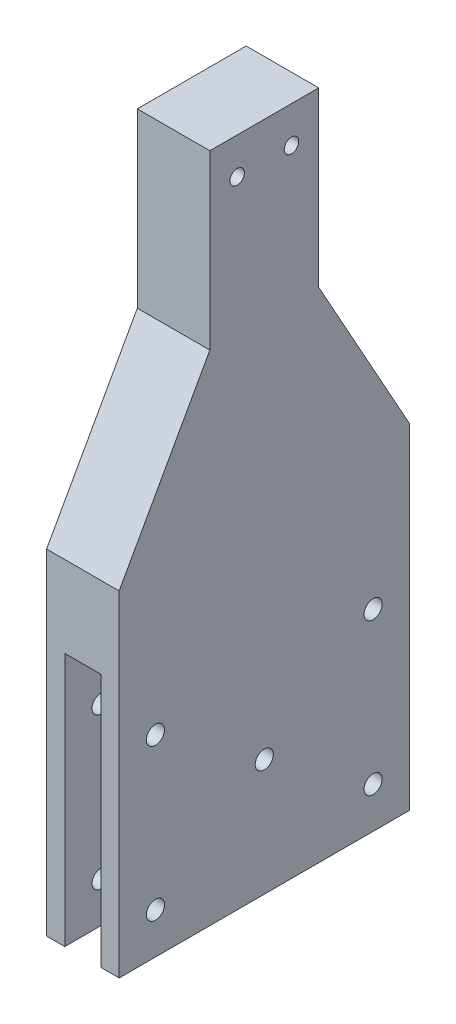
SolidWorks part; units mm, degrees
ref_plane "Plan de face" through (0, 0, 0) normal (0, 0, 1) x (1, 0, 0)
ref_plane "Plan de dessus" through (0, 0, 0) normal (0, 1, 0) x (1, 0, 0)
ref_plane "Plan de droite" through (0, 0, 0) normal (1, 0, 0) x (0, 0, -1)
sketch "Support Balise" plane through (0, 0, 0) normal (0, 0, 1) x (1, 0, 0)
  line L1 (0, 0) -> (20, 0)
  line L2 (0, 0) -> (0, 350)
  line L3 (0, 350) -> (20, 350)
  line L4 (20, 0) -> (20, 350)
  dimension "D1" = 20
  dimension "D2" = 350
extrude "Support balise bossage" add sketch "Support Balise" along normal blind 80
sketch "Esquisse3" plane through (0, 350, 0) normal (0, 1, 0) x (1, 0, 0)
  line L0 (20, 0) -> (20, -80)
  line L1 (20, -80) -> (-60, -80)
  line L2 (-60, -80) -> (-60, 0)
  line L3 (-60, 0) -> (20, 0)
  dimension "D1" = 80
extrude "Support Cheval enlevement de matiere" add sketch "Esquisse3" along normal blind 10
sketch "Esquisse8" plane through (0, 0, 80) normal (0, 0, 1) x (1, 0, 0)
  line L0 (0, 350) -> (0, 0) construction
  line L1 (5, 70) -> (15, 70)
  line L2 (5, 70) -> (5, 0)
  line L3 (5, 0) -> (15, 0)
  line L4 (15, 70) -> (15, 0)
  line L5 (20, 0) -> (20, 360) construction
  line L6 (0, 0) -> (20, 0) construction
  point P4 (5, 35)
  point P11 (10, 0)
  dimension "D1" = 5
  dimension "D2" = 5
  dimension "D3" = 0
  dimension "D4" = 70
extrude "Support Cheval" cut sketch "Esquisse8" against normal up to surface (80 mm away) up to face at (-13.3333, 236.6667, 0)
sketch "Serrage vis" plane through (5, 0, 0) normal (1, 0, 0) x (0, 0, -1)
  line L0 (-80, 0) -> (-80, 360) construction
  line L1 (0, 0) -> (0, 360) construction
  line L2 (-70, 53.0572) -> (-10, 11.2846) construction
  line L3 (-10, 53.0572) -> (-70, 11.2846) construction
  circle A0 centre (-70, 11.2846) radius 2.5
  circle A1 centre (-70, 53.0572) radius 2.5
  circle A2 centre (-10, 53.0572) radius 2.5
  circle A3 centre (-10, 11.2846) radius 2.5
  circle A4 centre (-40, 32.1709) radius 2.5
  dimension "D1" = 5
  dimension "D2" = 5
  dimension "D3" = 5
  dimension "D4" = 5
  dimension "D9" = 5
  dimension "D5" = 10
  dimension "D6" = 10
  dimension "D7" = 10
  dimension "D8" = 10
extrude "Vis" cut sketch "Serrage vis" against normal up to surface and the other way through all up to face at (0, 175, 40)
sketch "Design" plane through (20, 0, 0) normal (1, 0, 0) x (0, 0, -1)
  line L0 (-40, 360) -> (-40, 0) construction
  line L1 (-80, 360) -> (0, 360) construction
  line L2 (-80, 0) -> (0, 0) construction
  line L3 (-80, 360) -> (-55, 315)
  line L4 (0, 360) -> (-25, 315)
  line L5 (-80, 92.4061) -> (-55, 137.4061)
  line L6 (-80, 0) -> (-80, 360) construction
  line L7 (-25, 315) -> (-25, 137.4061)
  line L8 (-55, 315) -> (-55, 137.4061)
  line L9 (-80, 360) -> (-80, 92.4061)
  line L10 (0, 92.4061) -> (-25, 137.4061)
extrude "Enlèv. mat.-Extru.5" cut sketch "Design" against normal up to surface (20 mm away) contours L8 L3 L7 L5 | L10 L4 L7
fillet "Pour Impression" radius 15 2 edges at (0, 355, 2.7778) (0, 355, 77.2222)
sketch "Fixation pour assemblage" plane through (20, 0, 0) normal (1, 0, 0) x (0, 0, -1)
  line L0 (-55, 185) -> (-25, 185) construction
  line L1 (-55, 315) -> (-55, 137.4061) construction
  line L2 (-25, 315) -> (-25, 137.4061) construction
  line L3 (-80, 360) -> (0, 360) construction
  line L5 (-40, 360) -> (-40, 0) construction
  line L6 (-80, 0) -> (0, 0) construction
  circle A0 centre (-47.5, 195) radius 2
  circle A1 centre (-32.5, 195) radius 2
  circle A2 centre (-32.5, 175) radius 2
  circle A3 centre (-47.5, 175) radius 2
  dimension "D4" = 4
  dimension "D1" = 175
  dimension "D2" = 7.5
  dimension "D3" = 10
extrude "Vis pour Assemblage" cut sketch "Fixation pour assemblage" against normal up to surface (20 mm away) up to face at (0, 53.0572, 67.5)
sketch "Esquisse13" plane through (20, 0, 0) normal (1, 0, 0) x (0, 0, -1)
  line L0 (-55, 185) -> (-25, 185) construction
  line L1 (-55, 315) -> (-55, 137.4061) construction
  line L2 (-25, 315) -> (-25, 137.4061) construction
  line L3 (-80, 360) -> (0, 360) construction
  line L4 (-174.8974, 185) -> (122.4543, 185)
  line L5 (122.4543, 185) -> (122.4543, 440.4204)
  line L6 (122.4543, 440.4204) -> (-174.8974, 440.4204)
  line L7 (-174.8974, 440.4204) -> (-174.8974, 185)
  line L8 (-174.8974, 185) -> (-175.6186, 187.9975)
  circle M2 centre (-32.5, 195) radius 2
  circle M5 centre (-47.5, 195) radius 2
  line M12 (-25, 137.4061) -> (-25, 315)
  line M13 (-25, 315) -> (0, 360)
  line M14 (0, 360) -> (-80, 360)
  line M15 (-80, 360) -> (-55, 315)
  line M16 (-55, 315) -> (-55, 137.4061)
  dimension "D1" = 175
extrude "Enlèv. mat.-Extru.10" cut sketch "Esquisse13" against normal blind 463 contours L6 L7 L4 L5 M16 M15 M14 M13 M12 | L4 M16 M12 M13 M14 M15 M2 M5
